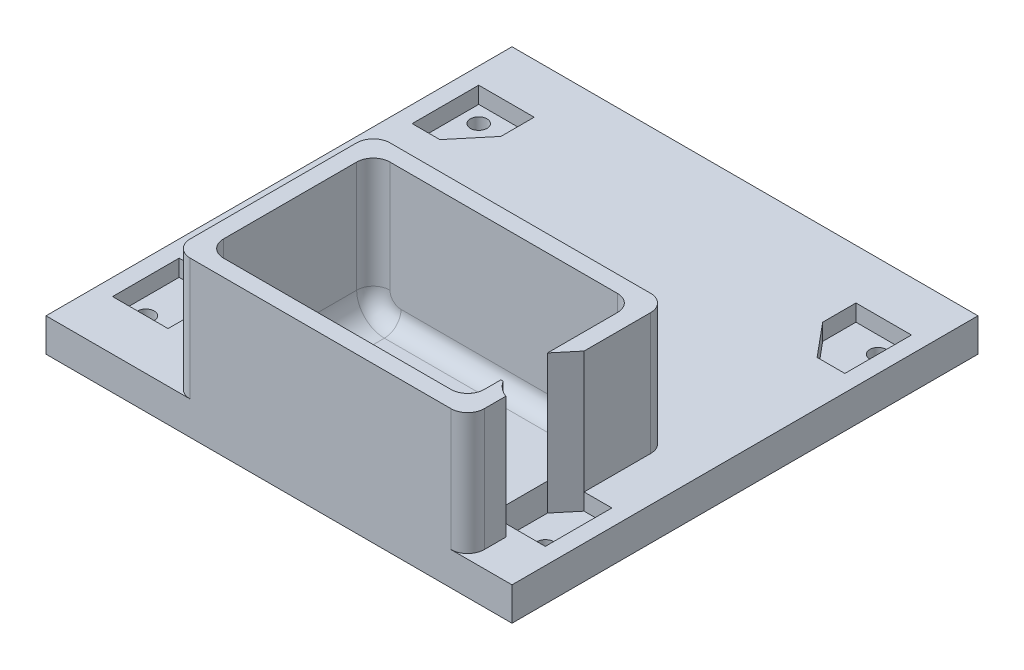
SolidWorks part; units mm, degrees
other "Markup1"
sketch "Sketch7"
sketch "Sketch12" plane through (84, 28, 0) normal (0.1424, 0.9893, 0.0306) x (0.9898, -0.1423, -0.003)
material "PVB"
ref_plane "Front Plane" through (0, 0, 0) normal (0, 0, 1) x (1, 0, 0)
ref_plane "Top Plane" through (0, 0, 0) normal (0, 1, 0) x (1, 0, 0)
ref_plane "Right Plane" through (0, 0, 0) normal (1, 0, 0) x (0, 0, -1)
sketch "Sketch1" plane through (0, 0, 0) normal (0, 1, 0) x (1, 0, 0)
  line L1 (0, 0) -> (84, 0)
  line L2 (0, 0) -> (0, 84)
  line L3 (0, 84) -> (84, 84)
  line L4 (84, 0) -> (84, 84)
  dimension "D1" = 84
  dimension "D2" = 84
extrude "Boss-Extrude1" add sketch "Sketch1" along normal blind 6
sketch "Sketch2" plane through (0, 6, 0) normal (0, 1, 0) x (1, 0, 0)
  line L0 (84, 84) -> (0, 84) construction
  line L1 (0, 84) -> (0, 0) construction
  line L2 (0, 0) -> (84, 0) construction
  line L3 (84, 0) -> (84, 84) construction
  circle A0 centre (6, 72) radius 1.5
  circle A1 centre (6, 12) radius 1.5
  circle A2 centre (78, 12) radius 1.5
  circle A3 centre (78, 72) radius 1.5
  dimension "D1" = 3
  dimension "D2" = 3
  dimension "D3" = 3
  dimension "D4" = 3
  dimension "D6" = 6
  dimension "D7" = 12
  dimension "D8" = 6
  dimension "D9" = 6
  dimension "D10" = 12
  dimension "D11" = 6
  dimension "D5" = 12
  dimension "D12" = 12
extrude "Cut-Extrude1" cut sketch "Sketch2" against normal through all
ref_plane "Plane1" through (0, 0, -42) normal (0, 0, 1) x (1, 0, 0)
sketch "Sketch4" plane through (0, 6, 0) normal (0, 1, 0) x (1, 0, 0)
  line L0 (3, 21) -> (3, 9)
  line L1 (3, 9) -> (13, 9)
  line L2 (13, 15) -> (8, 21)
  line L3 (3, 21) -> (8, 21)
  line L4 (8, 21) -> (13, 15)
  line L5 (13, 15) -> (13, 9)
  line L6 (0, 84) -> (0, 0) construction
  line L7 (0, 0) -> (84, 0) construction
  circle A0 centre (6, 12) radius 1.5
  circle A1 centre (6, 12) radius 1.5 construction
  circle M21 centre (6, 12) radius 1.5
  dimension "D1" = 3
  dimension "D2" = 9
  dimension "D3" = 12
  dimension "D4" = 10
  dimension "D5" = 6
  dimension "D6" = 5
extrude "Cut-Extrude4" cut sketch "Sketch4" against normal blind 3 contours L5 L2 L3 L0 L1 M21 region at (7.6338, 6, -14.6039)
mirror "Mirror2" about plane through (0, 0, -42) normal (0, 0, 1) of "Cut-Extrude4"
ref_plane "Plane2" through (42, 0, 0) normal (-1, 0, 0) x (0, 0, 1)
mirror "Mirror3" about plane through (42, 0, 0) normal (-1, 0, 0) of "Mirror2"
sketch "Sketch5" plane through (0, 6, 0) normal (0, 1, 0) x (1, 0, 0)
  line L0 (23, 36) -> (23, 0)
  line L1 (23, 36) -> (76, 36)
  line L2 (23, 0) -> (76, 0)
  line L3 (76, 36) -> (76, 0)
  line L4 (23, 36) -> (76, 0) construction
  line L5 (23, 0) -> (76, 36) construction
  line L7 (42, 3.3) -> (42, -3.3) construction
  line L12 (0, 0) -> (84, 0) construction
  point P1 (49.5, 18)
  dimension "D1" = 53
  dimension "D2" = 36
  dimension "D3" = 7.5
extrude "Boss-Extrude2" add sketch "Sketch5" along normal blind 22
sketch "Sketch6" plane through (0, 28, 0) normal (0, 1, 0) x (1, 0, 0)
  line L14 (73, 33) -> (26, 33)
  line L15 (26, 33) -> (26, 3)
  line L16 (26, 3) -> (73, 3)
  line L17 (73, 3) -> (73, 33)
  line L18 (73, 33) -> (26, 33)
  line L19 (26, 33) -> (26, 3)
  line L20 (26, 3) -> (73, 3)
  line L21 (73, 3) -> (73, 33)
  dimension "D1" = 3
extrude "Cut-Extrude5" cut sketch "Sketch6" against normal blind 25
fillet "Fillet1" radius 3 10 edges at (73, 15.5, -33) (26, 15.5, -33) (73, 15.5, -3) (26, 15.5, -3) (23, 17, -36) (76, 17, 0) (76, 17, -36) (23, 17, 0) (49.5, 3, -3) (49.5, 3, -33)
fillet "Fillet2" radius 5 7 edges at (26.8787, 3.8787, -3.8787) (26.8787, 3.8787, -32.1213) (72.1213, 3.8787, -32.1213) (72.1213, 3.8787, -3.8787) (73, 3, -23.7) (73, 3, -7.5) (26, 3, -18)
sketch "Sketch8" plane through (0, 28, 0) normal (0, 1, 0) x (1, 0, 0)
  line L0 (81, 21) -> (81, 9) construction
  line L1 (81, 9) -> (68, 9) construction
  line L2 (68, 11.4) -> (76, 21) construction
  line L3 (81, 21) -> (76, 21) construction
  line L4 (73, 36) -> (26, 36)
  line L5 (23, 33) -> (23, 3)
  line L6 (26, 0) -> (73, 0)
  line L7 (76, 3) -> (76, 33)
  line L8 (73, 36) -> (26, 36)
  line L9 (23, 33) -> (23, 3)
  line L10 (26, 0) -> (73, 0)
  line L11 (76, 3) -> (76, 33)
  line L12 (81, 21) -> (81, 9)
  line L13 (81, 9) -> (68, 9)
  line L14 (68, 11.4) -> (76, 21)
  line L15 (81, 21) -> (76, 21)
  line L16 (68, 11.4) -> (68, 9)
  circle A0 centre (78, 12) radius 1.5 construction
  circle A1 centre (78, 12) radius 1.5
  circle A2 centre (78, 12) radius 5.5
  arc A4 (26, 36) -> (23, 33) centre (26, 33) ccw
  arc A5 (23, 3) -> (26, 0) centre (26, 3) ccw
  arc A6 (73, 0) -> (76, 3) centre (73, 3) ccw
  arc A7 (76, 33) -> (73, 36) centre (73, 33) ccw
  arc A8 (26, 36) -> (23, 33) centre (26, 33) ccw
  arc A9 (23, 3) -> (26, 0) centre (26, 3) ccw
  arc A10 (73, 0) -> (76, 3) centre (73, 3) ccw
  arc A11 (76, 33) -> (73, 36) centre (73, 33) ccw
  line M17 (73, 30) -> (73, 6)
  dimension "D2" = 11
  dimension "D1" = 0
sketch "Sketch11" plane through (0, 3, 0) normal (0, 1, 0) x (1, 0, 0)
  line L0 (72.5826, 9) -> (68, 9) construction
  line L1 (68, 11.4) -> (72.5826, 16.8991) construction
  line L2 (73, 9) -> (68, 9)
  line L3 (68, 11.4) -> (73, 17.4)
  line L4 (73, 30) -> (73, 6) construction
  line L5 (73, 30) -> (73, 6) construction
  line L6 (73, 17.4) -> (73, 9)
  line L7 (68, 9) -> (68, 11.4)
extrude "Boss-Extrude3" add sketch "Sketch11" along normal up to surface contours L6 L2 L7 L3 up to face at (70.8236, 4.5868, -16.9523)
extrude "Cut-Extrude14" cut sketch "Sketch8" against normal up to surface (22 mm away) contours L11 A2 L13 M17 | L13 A2 L11 region at (74.6033, 28, -12.6035) region at (75.0415, 28, -8.2152) up to face at (76, 6, -69)
sketch "Sketch13" plane through (0, 3, 0) normal (0, 1, 0) x (1, 0, 0)
  line L5 (73, 17.4) -> (73, 9)
  line L6 (73, 9) -> (81, 9)
  line L7 (81, 9) -> (81, 21)
  line L8 (81, 21) -> (76, 21)
  line L9 (76, 21) -> (73, 17.4)
  line L10 (73, 17.4) -> (73, 9)
  line L11 (73, 9) -> (81, 9)
  line L12 (81, 9) -> (81, 21)
  line L13 (81, 21) -> (76, 21)
  line L14 (76, 21) -> (73, 17.4)
  dimension "D1" = 0
extrude "Cut-Extrude15" cut sketch "Sketch13" along normal through all
